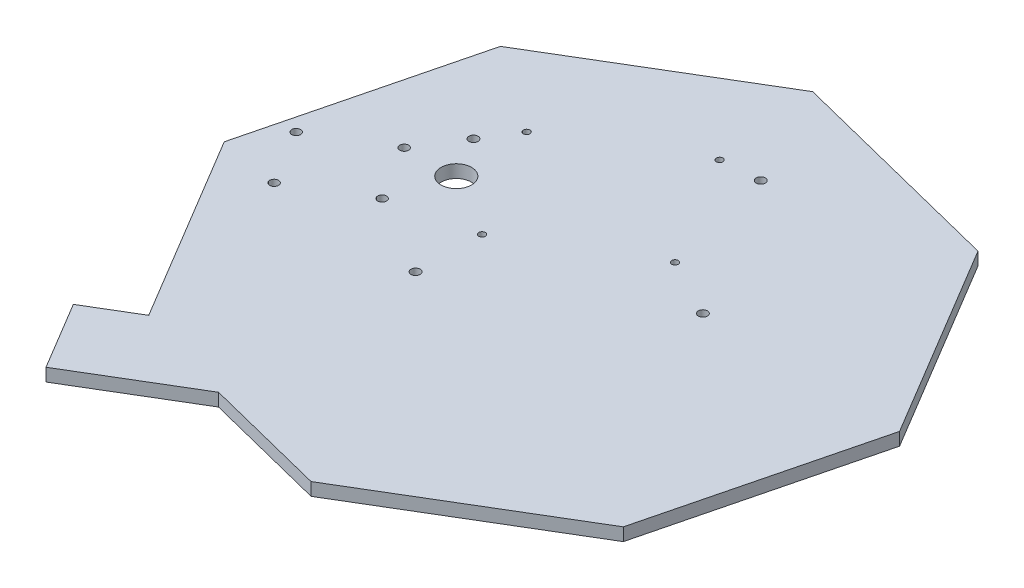
SolidWorks part; units mm, degrees
ref_plane "Front Plane" through (0, 0, 0) normal (0, 0, 1) x (1, 0, 0)
ref_plane "Top Plane" through (0, 0, 0) normal (0, 1, 0) x (1, 0, 0)
ref_plane "Right Plane" through (0, 0, 0) normal (1, 0, 0) x (0, 0, -1)
sketch "Sketch1" plane through (0, 0, 0) normal (0, 1, 0) x (1, 0, 0)
  line L1 (73.765, 99.3213) -> (-18.0711, 122.3905)
  line L2 (-18.0711, 122.3905) -> (-99.3213, 73.765)
  line L3 (-99.3213, 73.765) -> (-122.3905, -18.0711)
  line L4 (-122.3905, -18.0711) -> (-73.765, -99.3213)
  line L5 (-73.765, -99.3213) -> (18.0711, -122.3905)
  line L6 (18.0711, -122.3905) -> (99.3213, -73.765)
  line L7 (99.3213, -73.765) -> (122.3905, 18.0711)
  line L8 (122.3905, 18.0711) -> (73.765, 99.3213)
  circle A0 centre (0, 0) radius 114.3 construction
  dimension "baselength" = 228.6
extrude "Boss-Extrude2" add sketch "Sketch1" along normal blind 5.334
sketch "Sketch2" plane through (0, 5.334, 0) normal (0, 1, 0) x (-1, 0, 0)
  line L0 (75.5911, 96.27) -> (95.2066, 108.0093)
  line L1 (122.3905, 18.0711) -> (73.765, 99.3213) construction
  line L2 (95.2066, 108.0093) -> (78.2499, 136.3429)
  line L3 (78.2499, 136.3429) -> (33.3521, 109.473)
  line L4 (73.765, 99.3213) -> (-18.0711, 122.3905) construction
  line L5 (73.765, 99.3213) -> (75.5911, 96.27)
  line L6 (73.765, 99.3213) -> (33.3521, 109.473)
  dimension "D1" = 22.86
  dimension "D2" = 3.556
  dimension "D3" = 33.02
extrude "Boss-Extrude3" add sketch "Sketch2" against normal blind 5.334
sketch "Sketch3" plane through (0, 0, 0) normal (0, -1, 0) x (1, 0, 0)
  line L28 (122.3905, -18.0711) -> (99.3213, 73.765)
  circle A0 centre (-63.0561, -48.3878) radius 1.3716 construction
  circle A1 centre (-35.4167, -2.2041) radius 1.3716 construction
  circle A2 centre (14.7948, -32.2539) radius 1.3716 construction
  circle A3 centre (-12.8446, -78.4376) radius 1.3716 construction
  circle A4 centre (-63.0561, -48.3878) radius 1.3716
  circle A5 centre (-35.4167, -2.2041) radius 1.3716
  circle A6 centre (14.7948, -32.2539) radius 1.3716
  circle A7 centre (-12.8446, -78.4376) radius 1.3716
extrude "Cut-Extrude1" cut sketch "Sketch3" against normal through all contours A7 | A5 | A4 | A6 region at (-35.4167, 0, -2.2041) region at (-12.8446, 0, -78.4376)
sketch "Sketch4" plane through (0, 0, 0) normal (0, -1, 0) x (1, 0, 0)
  circle A0 centre (-61.7374, -17.8145) radius 6.35 construction
  circle A1 centre (-61.7374, -17.8145) radius 6.35
extrude "Cut-Extrude2" cut sketch "Sketch4" against normal through all
sketch "Sketch5" plane through (0, 0, 0) normal (0, -1, 0) x (1, 0, 0)
  circle A0 centre (3.1391, -79.5818) radius 1.905 construction
  circle A1 centre (-71.618, -34.8422) radius 1.905 construction
  circle A2 centre (39.009, -19.6454) radius 1.905 construction
  circle A3 centre (-35.7481, 25.0942) radius 1.905 construction
  circle A4 centre (3.1391, -79.5818) radius 1.905
  circle A5 centre (-71.618, -34.8422) radius 1.905
  circle A6 centre (39.009, -19.6454) radius 1.905
  circle A7 centre (-35.7481, 25.0942) radius 1.905
extrude "Cut-Extrude3" cut sketch "Sketch5" against normal through all
sketch "Sketch6" plane through (0, 0, 0) normal (0, -1, 0) x (1, 0, 0)
  circle A0 centre (-110.9327, -0.4075) radius 1.8415 construction
  circle A1 centre (-82.8171, -17.2338) radius 1.8415 construction
  circle A2 centre (-97.237, 22.4773) radius 1.8415 construction
  circle A3 centre (-69.1213, 5.651) radius 1.8415 construction
  circle A4 centre (-110.9327, -0.4075) radius 1.8415
  circle A5 centre (-82.8171, -17.2338) radius 1.8415
  circle A6 centre (-97.237, 22.4773) radius 1.8415
  circle A7 centre (-69.1213, 5.651) radius 1.8415
extrude "Cut-Extrude4" cut sketch "Sketch6" against normal through all
equation "\"baselength\"=9"
equation "\"material\"=\"GMaterial@Platform.assembly\""
equation "\"D1@Boss-Extrude2\" = \"material\""
equation "\"D1@Boss-Extrude3\" = \"material\""
